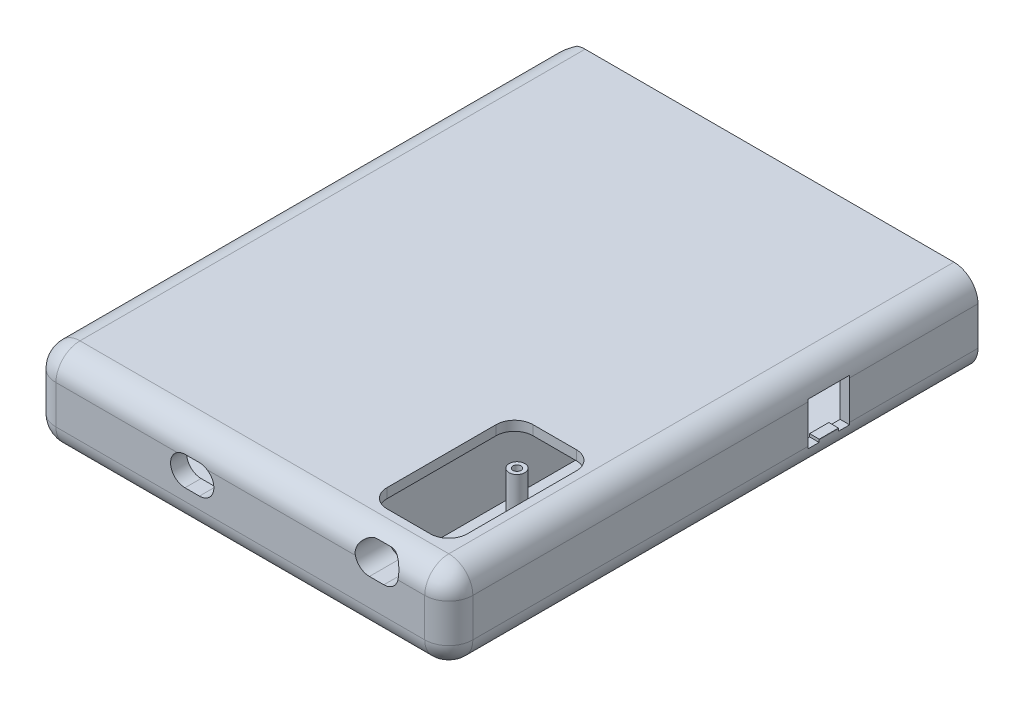
SolidWorks part; units mm, degrees
ref_plane "Front Plane" through (0, 0, 0) normal (0, 0, 1) x (1, 0, 0)
ref_plane "Top Plane" through (0, 0, 0) normal (0, 1, 0) x (1, 0, 0)
ref_plane "Right Plane" through (0, 0, 0) normal (1, 0, 0) x (0, 0, -1)
sketch "Sketch1" plane through (0, 0, 0) normal (0, 1, 0) x (1, 0, 0)
  line L1 (0, 0) -> (130, 0)
  line L2 (0, 0) -> (0, -157.5)
  line L3 (7.5, -165) -> (122.5, -165)
  line L4 (130, 0) -> (130, -157.5)
  arc A0 (122.5, -165) -> (130, -157.5) centre (122.5, -157.5) ccw
  arc A1 (0, -157.5) -> (7.5, -165) centre (7.5, -157.5) ccw
  point P15 (130, -165)
  point P18 (0, -165)
  dimension "D3" = 7.5
  dimension "D1" = 165
  dimension "D2" = 130
extrude "Boss-Extrude1" add sketch "Sketch1" along normal blind 27
sketch "Sketch2" plane through (0, 27, 0) normal (0, 1, 0) x (1, 0, 0)
  line L1 (10, 0) -> (90, 0)
  line L2 (10, 0) -> (10, -152.5)
  line L3 (17.5, -160) -> (82.5, -160)
  line L4 (90, 0) -> (90, -152.5)
  line L5 (0, 0) -> (0, -157.5) construction
  line L6 (7.5, -165) -> (122.5, -165) construction
  line L7 (130, 0) -> (0, 0) construction
  arc A0 (10, -152.5) -> (17.5, -160) centre (17.5, -152.5) ccw
  arc A1 (90, -152.5) -> (82.5, -160) centre (82.5, -152.5) cw
  dimension "D4" = 7.5
  dimension "D1" = 80
  dimension "D2" = 10
  dimension "D3" = 5
extrude "Cut-Extrude1" cut sketch "Sketch2" against normal blind 17 from offset 5 offset against normal yes
sketch "Sketch3" plane through (0, 0, 160) normal (0, 0, -1) x (-1, 0, 0)
  line L0 (-52.25, 15.7) -> (-47.75, 15.7) construction
  line L1 (-52.25, 20.2) -> (-47.75, 20.2)
  line L2 (-52.25, 11.2) -> (-47.75, 11.2)
  line L3 (-90, 15.7) -> (-10, 15.7) construction
  line L4 (-90, 5) -> (-90, 22) construction
  line L5 (-10, 5) -> (-10, 22) construction
  line L6 (-90, 22) -> (-10, 22) construction
  arc A0 (-52.25, 20.2) -> (-52.25, 11.2) centre (-52.25, 15.7) ccw
  arc A1 (-47.75, 11.2) -> (-47.75, 20.2) centre (-47.75, 15.7) ccw
  point P2 (-50, 15.7)
  point P13 (-50, 15.7)
  dimension "D2" = 13.5
  dimension "D1" = 9
  dimension "D4" = 6.3
extrude "Cut-Extrude2" cut sketch "Sketch3" against normal blind 10
fillet "Fillet2" radius 7.5 5 edges at (0, 0, 78.75) (2.1967, 0, 162.8033) (65, 0, 165) (127.8033, 0, 162.8033) (130, 0, 78.75)
fillet "Fillet3" radius 7.5 6 edges at (65, 27, 165) (127.8033, 27, 162.8033) (130, 27, 78.75) (50, 20.2, 165) (0, 27, 78.75) (2.1967, 27, 162.8033)
sketch "Sketch4" plane through (0, 5, 0) normal (0, 1, 0) x (1, 0, 0)
  line L0 (90, -152.5) -> (90, 0) construction
  line L1 (10, -60) -> (90, -60)
  line L2 (10, -60) -> (10, -160)
  line L3 (10, -160) -> (90, -160)
  line L4 (90, -60) -> (90, -160)
  line L6 (10, 0) -> (10, -152.5) construction
  line L7 (17.5, -160) -> (82.5, -160) construction
  dimension "D1" = 100
extrude "Boss-Extrude2" add sketch "Sketch4" along normal blind 3.5
sketch "Sketch5" plane through (0, 0, 0) normal (0, 0, -1) x (-1, 0, 0)
sketch "Sketch6" plane through (0, 0, 0) normal (0, 0, -1) x (-1, 0, 0)
  line L0 (0, 19.5) -> (0, 7.5) construction
  line L1 (-122.5, 27) -> (-7.5, 27) construction
  line L2 (-122.5, 0) -> (-7.5, 0) construction
  circle A0 centre (-5, 22) radius 2.2
  circle A1 centre (-5, 5) radius 2.2
  dimension "D1" = 4.4
  dimension "D2" = 4.4
  dimension "D3" = 5
  dimension "D4" = 5
  dimension "D5" = 5
chamfer "Chamfer6" distance 5 angle 45 1 edges at (0, 13.5, 0)
extrude "Cut-Extrude3" cut sketch "Sketch6" against normal blind 12
sketch "Sketch9" plane through (0, 27, 0) normal (0, 1, 0) x (1, 0, 0)
  line L1 (100.75, -109.5) -> (114.25, -109.5)
  line L2 (95, -115.25) -> (95, -149.25)
  line L3 (100.75, -155) -> (114.25, -155)
  line L4 (120, -115.25) -> (120, -149.25)
  line L8 (122.5, -157.5) -> (122.5, 0) construction
  line L11 (7.5, -157.5) -> (122.5, -157.5) construction
  arc A0 (120, -149.25) -> (114.25, -155) centre (114.25, -149.25) cw
  arc A1 (100.75, -155) -> (95, -149.25) centre (100.75, -149.25) cw
  arc A2 (95, -115.25) -> (100.75, -109.5) centre (100.75, -115.25) cw
  arc A3 (114.25, -109.5) -> (120, -115.25) centre (114.25, -115.25) cw
  point P6 (120, -155)
  point P9 (95, -155)
  point P14 (120, -109.5)
  dimension "D3" = 5.75
  dimension "D1" = 45.5
  dimension "D2" = 25
  dimension "D4" = 2.5
  dimension "D5" = 2.5
extrude "Cut-Extrude4" cut sketch "Sketch9" against normal blind 22
sketch "Sketch11" plane through (0, 0, 0) normal (0, 0, -1) x (-1, 0, 0)
  line L0 (-90, 5) -> (-90, 22) construction
  line L2 (-127, 16.5) -> (-127, 3)
  line L3 (-127, 3) -> (-93, 3)
  line L4 (-93, 24) -> (-93, 3)
  line L5 (-127, 16.5) -> (-127, 24)
  line L7 (-127, 24) -> (-93, 24)
  point P8 (-127, 24)
  dimension "D5" = 21
  dimension "D1" = 3
  dimension "D6" = 34
extrude "Cut-Extrude5" cut sketch "Sketch11" against normal up to surface (155 mm away) up to face at (107.5, 16, 155)
sketch "Sketch12" plane through (0, 3, 0) normal (0, 1, 0) x (1, 0, 0)
  line L0 (99, -112.75) -> (99, -151.75) construction
  line L1 (99, -151.75) -> (116, -151.75) construction
  line L2 (116, -151.75) -> (116, -108.6799) construction
  line L6 (100.75, -155) -> (114.25, -155) construction
  line L8 (99, -112.75) -> (116, -112.75) construction
  line L9 (95, -115.25) -> (95, -149.25) construction
  circle A0 centre (99, -112.75) radius 1.25
  circle A1 centre (116, -112.75) radius 1.25
  circle A2 centre (99, -151.75) radius 1.25
  circle A3 centre (116, -151.75) radius 1.25
  circle A4 centre (99, -112.75) radius 2.45
  circle A5 centre (116, -112.75) radius 2.45
  circle A7 centre (99, -151.75) radius 2.45
  circle A8 centre (116, -151.75) radius 2.45
  point P10 (99, -112.75)
  point P14 (107.5, -155)
  point P15 (107.5, -151.75)
  point P16 (95, -132.25)
  point P17 (99, -132.25)
  dimension "D3" = 2.5
  dimension "D4" = 2.5
  dimension "D5" = 2.5
  dimension "D6" = 2.5
  dimension "D7" = 4.9
  dimension "D8" = 4.9
  dimension "D9" = 4.9
  dimension "D10" = 4.9
  dimension "D1" = 17
  dimension "D2" = 39
extrude "Boss-Extrude4" add sketch "Sketch12" along normal blind 13 and the other way up to surface (3 mm away) other way up to face at (65, 0, 78.75)
sketch "Sketch14" plane through (0, 3, 0) normal (0, 1, 0) x (1, 0, 0)
  circle A0 centre (99, -112.75) radius 1.8
  circle A1 centre (116, -112.75) radius 1.8
  circle A2 centre (99, -151.75) radius 1.8
  circle A3 centre (116, -151.75) radius 1.8
  dimension "D1" = 3.6
  dimension "D2" = 3.6
  dimension "D3" = 3.6
  dimension "D4" = 3.6
extrude "Cut-Extrude6" cut sketch "Sketch14" against normal up to surface (3 mm away) up to face at (65, 0, 78.75)
sketch "Sketch15" plane through (0, 0, 0) normal (0, -1, 0) x (1, 0, 0)
  circle A0 centre (99, 151.75) radius 2.25
  circle A1 centre (116, 151.75) radius 2.25
  circle A2 centre (116, 112.75) radius 2.25
  circle A3 centre (99, 112.75) radius 2.25
  dimension "D1" = 4.5
  dimension "D2" = 2
  dimension "D3" = 2
extrude "Cut-Extrude7" cut sketch "Sketch15" against normal blind 2
chamfer "Chamfer7" distance 45 angle 5 1 edges at (50, 8.5, 60)
sketch "Sketch16" plane through (0, 0, 165) normal (0, 0, 1) x (1, 0, 0)
  line L0 (105.25, 20.5) -> (109.75, 20.5) construction
  line L1 (105.25, 25) -> (109.75, 25)
  line L2 (105.25, 16) -> (109.75, 16)
  line L3 (66.8102, 20.5) -> (148.1898, 20.5) construction
  line L8 (7.5, 27) -> (122.5, 27) construction
  line L9 (127, 13.5) -> (93, 13.5) construction
  line L10 (127, 24) -> (127, 3) construction
  line L13 (122.5, 19.5) -> (122.5, 7.5) construction
  arc A0 (105.25, 25) -> (105.25, 16) centre (105.25, 20.5) ccw
  arc A1 (109.75, 16) -> (109.75, 25) centre (109.75, 20.5) ccw
  point P2 (107.5, 20.5)
  point P13 (107.5, 20.5)
  dimension "D2" = 13.5
  dimension "D3" = 6.5
  dimension "D1" = 9
  dimension "D4" = 15
extrude "Cut-Extrude8" cut sketch "Sketch16" against normal up to surface (10 mm away) up to face at (108.75, 19.5, 155)
ref_plane "Plane17" through (0, 0, 0) normal (0, 0, -1) x (-1, 0, 0)
sketch "Sketch18" plane through (0, 0, 0) normal (0, 0, -1) x (-1, 0, 0)
  line L1 (-127, 3) -> (-122.25, 3)
  line L2 (-127, 3) -> (-127, 15.5)
  line L3 (-127, 15.5) -> (-122.25, 15.5)
  line L4 (-122.25, 3) -> (-122.25, 15.5)
  line L5 (-93, 3) -> (-97.75, 3)
  line L6 (-93, 3) -> (-93, 15.5)
  line L7 (-93, 15.5) -> (-97.75, 15.5)
  line L8 (-97.75, 3) -> (-97.75, 15.5)
  line L10 (-127, 3) -> (-93, 3) construction
  circle A0 centre (-124, 9.25) radius 0.75
  circle A1 centre (-96, 9.25) radius 0.75
  point P17 (-127, 9.25)
  point P18 (-93, 9.25)
  dimension "D3" = 1.5
  dimension "D4" = 1.5
  dimension "D1" = 24.5
  dimension "D2" = 12.5
  dimension "D5" = 1.75
  dimension "D6" = 1.75
extrude "Boss-Extrude5" add sketch "Sketch18" against normal blind 15 from offset 17.5 offset against normal yes
sketch "Sketch19" plane through (0, 0, 0) normal (0, 0, -1) x (-1, 0, 0)
  line L0 (-127, 24) -> (-127, 3) construction
  line L1 (-124.75, 24) -> (-121.25, 24)
  line L2 (-124.75, 24) -> (-124.75, 16)
  line L3 (-124.75, 16) -> (-121.25, 16)
  line L4 (-121.25, 24) -> (-121.25, 16)
  line L5 (-93, 24) -> (-127, 24) construction
  dimension "D1" = 8
  dimension "D2" = 3.5
  dimension "D3" = 2.25
extrude "Boss-Extrude6" add sketch "Sketch19" against normal blind 3 from offset 11 offset against normal yes
chamfer "Chamfer9" distance 8 angle 75 1 edges at (123, 24, 14)
chamfer "Chamfer8" distance 10 angle 29 2 edges at (97.75, 9.25, 32.5) (122.25, 9.25, 32.5)
sketch "Sketch20" plane through (0, 0, 0) normal (0, 0, -1) x (-1, 0, 0)
  line L0 (-93, 24) -> (-100.75, 24) construction
  line L1 (-116.5, 24) -> (-111, 24)
  line L2 (-116.5, 24) -> (-116.5, 18)
  line L3 (-116.5, 18) -> (-111, 18)
  line L4 (-111, 24) -> (-111, 18)
  line L5 (-93, 3) -> (-93, 24) construction
  dimension "D1" = 5.5
  dimension "D2" = 6
  dimension "D3" = 18
extrude "Boss-Extrude7" add sketch "Sketch20" against normal blind 10 from offset 4.5 offset against normal yes
chamfer "Chamfer11" distance 6 angle 76 1 edges at (113.75, 24, 14.5)
sketch "Sketch21" plane through (130, 0, 0) normal (1, 0, 0) x (0, 0, -1)
  line L0 (-49.5, 6.8) -> (-49.5, 7.7)
  line L1 (-53, 20.2) -> (-40, 20.2)
  line L2 (-53, 20.2) -> (-53, 6.8)
  line L3 (-53, 6.8) -> (-49.5, 6.8)
  line L4 (-40, 20.2) -> (-40, 6.8)
  line L5 (-49.5, 7.7) -> (-43.5, 7.7)
  line L6 (-43.5, 7.7) -> (-43.5, 6.8)
  line L7 (-43.5, 6.8) -> (-40, 6.8)
  line L8 (0, 19.5) -> (0, 7.5) construction
  point P10 (0, 13.5)
  point P11 (-40, 13.5)
  dimension "D1" = 13.4
  dimension "D2" = 13
  dimension "D3" = 6
  dimension "D4" = 12.5
  dimension "D5" = 40
extrude "Cut-Extrude9" cut sketch "Sketch21" against normal up to surface (3 mm away) up to face at (127, 11.375, 50.8923)
sketch "Sketch22" plane through (0, 0, 160) normal (0, 0, -1) x (-1, 0, 0)
  line L5 (-90, 22) -> (-10, 22) construction
  circle A0 centre (-74.75, 14.75) radius 2.5
  circle A1 centre (-25.25, 14.75) radius 2.5
  arc A5 (-52.25, 20.2) -> (-52.25, 11.2) centre (-52.25, 15.7) ccw construction
  arc A6 (-47.75, 11.2) -> (-47.75, 20.2) centre (-47.75, 15.7) ccw construction
  dimension "D1" = 5
  dimension "D2" = 5
  dimension "D6" = 18
  dimension "D3" = 7.25
  dimension "D4" = 7.25
  dimension "D5" = 18
extrude "Cut-Extrude10" cut sketch "Sketch22" against normal blind 3
